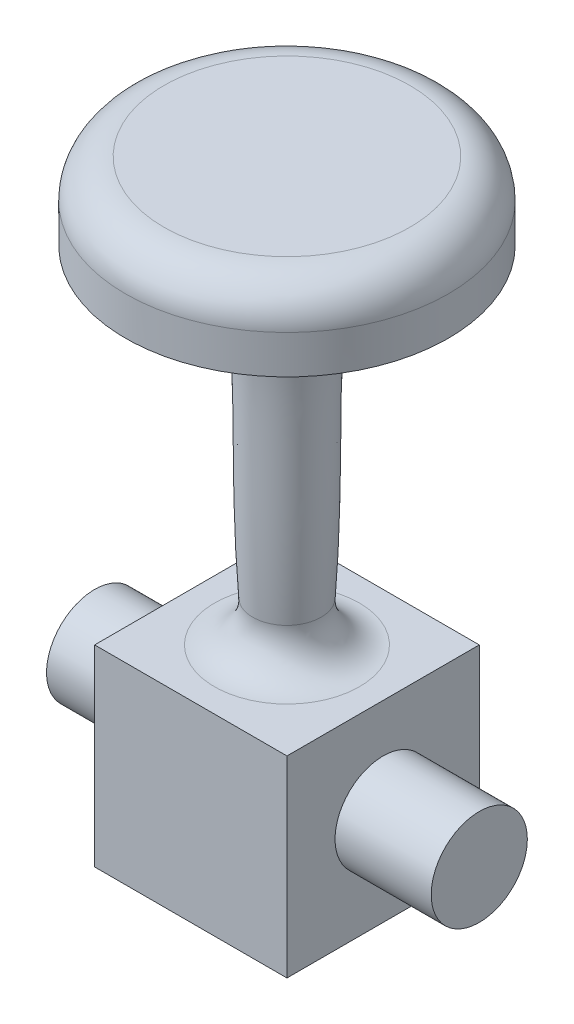
SolidWorks part; units mm, degrees
ref_plane "Front Plane" through (0, 0, 0) normal (0, 0, 1) x (1, 0, 0)
ref_plane "Top Plane" through (0, 0, 0) normal (0, 1, 0) x (1, 0, 0)
ref_plane "Right Plane" through (0, 0, 0) normal (1, 0, 0) x (0, 0, -1)
sketch "Sketch2" plane through (0, 0, 0) normal (1, 0, 0) x (0, 0, -1)
  line L1 (0, 0) -> (12.7, 0)
  line L2 (0, 0) -> (0, 12.7)
  line L3 (0, 12.7) -> (12.7, 12.7)
  line L4 (12.7, 0) -> (12.7, 12.7)
  dimension "D1" = 12.7
  dimension "D2" = 12.7
extrude "central box" add sketch "Sketch2" along normal blind 12.7
ref_point "center for extrusion of nibbles"
sketch "Sketch4" plane through (12.7, 0, 0) normal (1, 0, 0) x (0, 0, -1)
  circle A0 centre (6.35, 6.35) radius 3.175
  dimension "D1" = 6.35
extrude "nibbles" add sketch "Sketch4" along normal blind 6.35 and the other way blind 19.05
ref_point "stick extrusion spot"
ref_plane "stick drawin' plane" through (0, 0, -6.35) normal (0, 0, 1) x (1, 0, 0)
sketch "Sketch6" plane through (0, 0, -6.35) normal (0, 0, 1) x (1, 0, 0)
  line L0 (6.35, 12.7) -> (6.35, 40.64)
  line L1 (6.35, 40.64) -> (17.0076, 40.64)
  line L2 (17.0076, 40.64) -> (17.0076, 35.56)
  line L3 (6.35, 12.7) -> (8.382, 12.7)
  spline S0 degree 3 poles (17.0076, 35.56) (6.0875, 40.535) (9.9527, 28.575) (8.382, 12.7) knots 0 0 0 0 1 1 1 1
  dimension "D1" = 2.032
  dimension "D2" = 27.94
  dimension "D3" = 5.08
revolve "stick" add sketch "Sketch6" angle 360 about L0
fillet "yay, rounded" radius 2.54 2 edges at (6.35, 12.7, -8.382) (6.35, 40.64, -17.0076)
